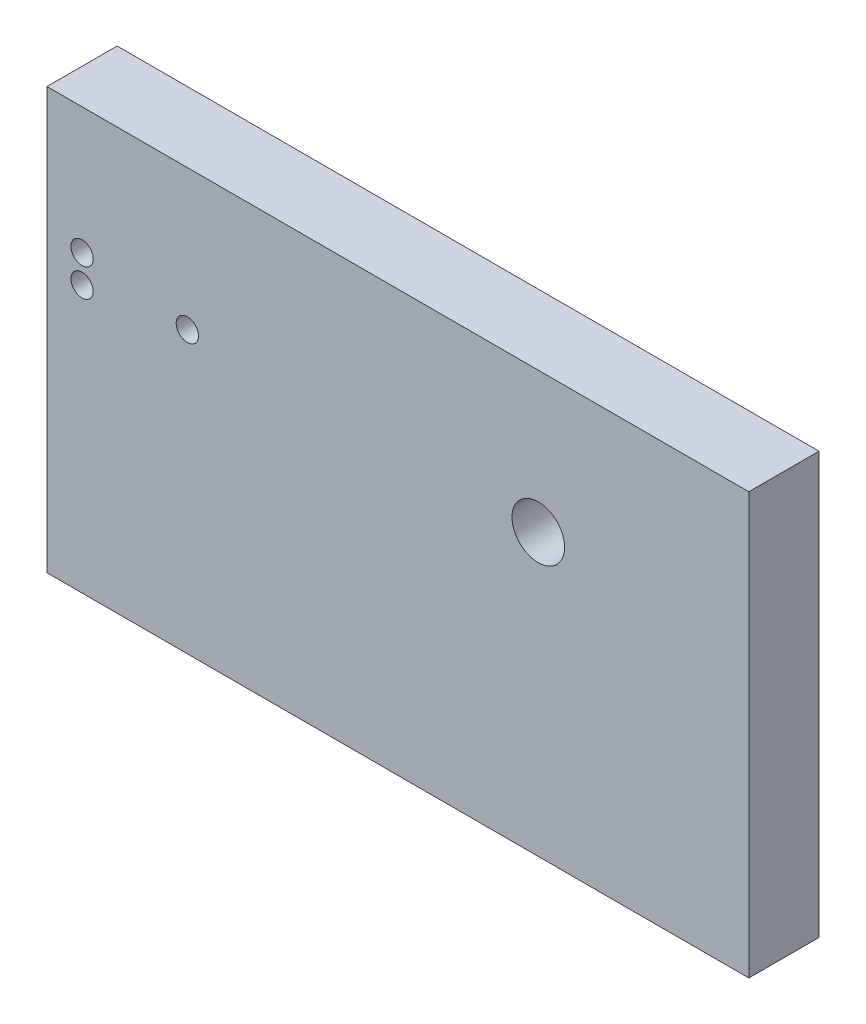
SolidWorks part; units mm, degrees
ref_plane "Front Plane" through (0, 0, 0) normal (0, 0, 1) x (1, 0, 0)
ref_plane "Top Plane" through (0, 0, 0) normal (0, 1, 0) x (1, 0, 0)
ref_plane "Right Plane" through (0, 0, 0) normal (1, 0, 0) x (0, 0, -1)
sketch "Sketch1" plane through (0, 0, 0) normal (0, 0, 1) x (1, 0, 0)
  line L1 (0, 0) -> (127, 0)
  line L2 (0, 0) -> (0, 76.2)
  line L3 (0, 76.2) -> (127, 76.2)
  line L4 (127, 0) -> (127, 76.2)
  dimension "D1" = 127
  dimension "D2" = 76.2
extrude "Boss-Extrude1" add sketch "Sketch1" along normal blind 12.7 contours L2 L1 L4 L3
hole_wizard "1/32 (0.159) Diameter Hole1" positions "Sketch5" profile "Sketch6" hole size "1/32" standard "ANSI Inch" end condition through all
sketch "Sketch5" plane through (0, 0, 12.7) normal (0, 0, 1) x (1, 0, 0)
  line L0 (0, 0) -> (0, 76.2) construction
  line L1 (0, 0) -> (127, 0) construction
  point P0 (25.4, 50.8)
  point P1 (28.7698, 54.853)
  dimension "D1" = 25.4
  dimension "D2" = 50.8
sketch "Sketch6" plane through (25.4, 50.8, 12.7) normal (1, 0, 0) x (0, -1, 0)
  line L0 (0, 0) -> (0, 12.7)
  line L1 (0, 12.7) -> (2.0193, 12.7)
  line L2 (2.0193, 12.7) -> (2.0193, 0)
  line L5 (2.0193, 0) -> (0, 0)
  line L11 (0, -6.35) -> (0, 107.95) construction
  dimension "Thru Hole Dia." = 4.0386
  dimension "Thru Hole Depth" = 12.7
hole_wizard "#10-32 Tapped Hole1" positions "Sketch9" profile "Sketch10" tap size "#10-32" standard "ANSI Inch"
sketch "Sketch9" plane through (0, 0, 0) normal (0, -1, 0) x (-1, 0, 0)
  line L0 (0, -12.7) -> (-127, -12.7) construction
  line L1 (-19.05, -6.35) -> (-107.95, -6.35) construction
  line L3 (-63.5, -12.7) -> (-63.5, 0) construction
  line L4 (0, 0) -> (-127, 0) construction
  point P0 (-19.05, -6.35)
  point P2 (-107.95, -6.35)
  point P21 (-63.5, -6.35)
  point P22 (-107.95, -6.35)
  dimension "D1" = 6.35
  dimension "D2" = 88.9
sketch "Sketch10" plane through (19.05, 0, 6.35) normal (1, 0, 0) x (0, 0, -1)
  line L0 (0, 0) -> (0, 12.7)
  line L1 (0, 12.7) -> (2.0193, 11.4867)
  line L2 (2.0193, 11.4867) -> (2.0193, 0)
  line L5 (2.0193, 0) -> (0, 0)
  line L10 (0, 12.7) -> (-2.0193, 11.4867) construction
  line L11 (0, -6.35) -> (0, 107.95) construction
  dimension "Tap Drill Dia." = 4.0386
  dimension "Tap Drill Depth" = 12.7
  dimension "Drill Angle" = 118
cosmetic thread "Hole Thread3" parameters "D1"=9.652, "D2"=4.826
cosmetic thread "Hole Thread4" parameters "D1"=9.652, "D2"=4.826
hole_wizard "3/8 (0.375) Diameter Hole1" positions "Sketch14" profile "Sketch15" hole size "3/8" standard "ANSI Inch" end condition through all
sketch "Sketch14" plane through (0, 0, 12.7) normal (0, 0, 1) x (1, 0, 0)
  line L0 (0, 0) -> (127, 0) construction
  line L1 (0, 0) -> (0, 76.2) construction
  point P0 (88.9, 50.8)
  dimension "D1" = 50.8
  dimension "D2" = 88.9
sketch "Sketch15" plane through (88.9, 50.8, 12.7) normal (1, 0, 0) x (0, -1, 0)
  line L0 (0, 0) -> (0, 12.7)
  line L1 (0, 12.7) -> (4.7625, 12.7)
  line L2 (4.7625, 12.7) -> (4.7625, 0)
  line L5 (4.7625, 0) -> (0, 0)
  line L11 (0, -6.35) -> (0, 107.95) construction
  dimension "Thru Hole Dia." = 9.525
  dimension "Thru Hole Depth" = 12.7
hole_wizard "#10-32 Tapped Hole2" positions "Sketch16" profile "Sketch17" tap size "#10-32" standard "ANSI Inch"
sketch "Sketch16" plane through (0, 0, 12.7) normal (0, 0, 1) x (1, 0, 0)
  line L0 (0, 0) -> (0, 76.2) construction
  line L1 (0, 0) -> (127, 0) construction
  point P0 (6.35, 48.26)
  dimension "D1" = 6.35
  dimension "D2" = 48.26
sketch "Sketch17" plane through (6.35, 48.26, 12.7) normal (1, 0, 0) x (0, -1, 0)
  line L0 (0, 0) -> (0, 15.6913)
  line L1 (0, 15.6913) -> (2.0193, 14.478)
  line L2 (2.0193, 14.478) -> (2.0193, 0)
  line L5 (2.0193, 0) -> (0, 0)
  line L10 (0, 15.6913) -> (-2.0193, 14.478) construction
  line L11 (0, -6.35) -> (0, 107.95) construction
  dimension "Tap Drill Dia." = 4.0386
  dimension "Tap Drill Depth" = 14.478
  dimension "Drill Angle" = 118
cosmetic thread "Hole Thread5" parameters "D1"=9.652, "D2"=4.826
hole_wizard "#21 (0.159) Diameter Hole1" positions "Sketch18" profile "Sketch19" hole size "#21" standard "ANSI Inch"
sketch "Sketch18" plane through (0, 0, 12.7) normal (0, 0, 1) x (1, 0, 0)
  line L0 (0, 0) -> (0, 76.2) construction
  line L1 (0, 0) -> (127, 0) construction
  point P0 (6.35, 53.34)
  dimension "D1" = 6.35
  dimension "D2" = 53.34
sketch "Sketch19" plane through (6.35, 53.34, 12.7) normal (1, 0, 0) x (0, -1, 0)
  line L0 (0, 0) -> (0, 15.6913)
  line L1 (0, 15.6913) -> (2.0193, 14.478)
  line L2 (2.0193, 14.478) -> (2.0193, 0)
  line L5 (2.0193, 0) -> (0, 0)
  line L10 (0, 15.6913) -> (-2.0193, 14.478) construction
  line L11 (0, -6.35) -> (0, 107.95) construction
  dimension "Hole Dia." = 4.0386
  dimension "Hole Depth" = 14.478
  dimension "Drill Angle" = 118
